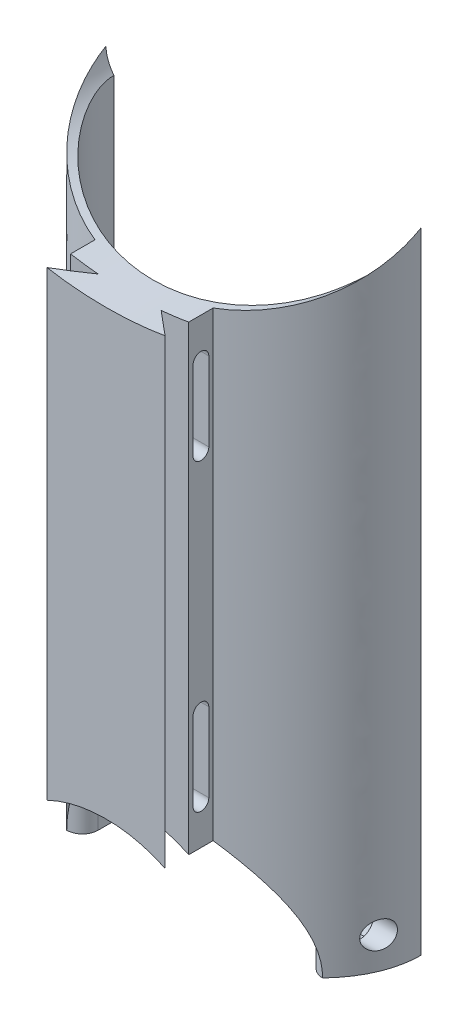
SolidWorks part; units mm, degrees
material "PLA"
ref_plane "Front Plane" through (0, 0, 0) normal (0, 0, 1) x (1, 0, 0)
ref_plane "Top Plane" through (0, 0, 0) normal (0, 1, 0) x (1, 0, 0)
ref_plane "Right Plane" through (0, 0, 0) normal (1, 0, 0) x (0, 0, -1)
sketch "Sketch1" plane through (0, 0, 0) normal (0, 1, 0) x (1, 0, 0)
  ellipse E0 centre (0, 0) end of major axis (25.4, 0) minor radius 19.05
  dimension "D1" = 50.8
  dimension "D2" = 38.1
extrude "Boss-Extrude1" add sketch "Sketch1" along normal blind 101.6 contours E0
shell "Shell1" thickness 1.27 removed face at (25.4, 101.6, 0) removed face at (25.4, 0, 0)
sketch "Sketch3" plane through (0, 0, 0) normal (0, 0, 1) x (1, 0, 0)
  line L1 (29.1836, -15.0653) -> (-40.8926, -15.0653)
  line L2 (29.1836, -15.0653) -> (29.1836, 142.3871)
  line L3 (29.1836, 142.3871) -> (-40.8926, 142.3871)
  line L4 (-40.8926, -15.0653) -> (-40.8926, 142.3871)
extrude "Cut-Extrude1" cut sketch "Sketch3" against normal up to surface up to face at (25.4, 101.6, 0)
ref_plane "Plane4" through (0, 0, 19.05) normal (0, 0, 1) x (1, 0, 0)
sketch "Sketch4" plane through (0, 0, 19.05) normal (0, 0, 1) x (1, 0, 0)
  line L1 (9.525, 101.6) -> (-9.525, 101.6)
  line L2 (9.525, 101.6) -> (9.525, 0)
  line L3 (9.525, 0) -> (-9.525, 0)
  line L4 (-9.525, 101.6) -> (-9.525, 0)
  line L6 (25.4, 101.6) -> (25.4, 0) construction
  line L7 (-25.4, 0) -> (25.4, 0) construction
  line L8 (25.4, 101.6) -> (-25.4, 101.6) construction
  dimension "D1" = 19.05
  dimension "D4" = 15.875
extrude "Boss-Extrude2" add sketch "Sketch4" against normal up to surface (1.3902 mm away) up to face at (0, 50.8, 9.525)
sketch "Sketch6" plane through (0, 0, 19.05) normal (0, 0, 1) x (1, 0, 0)
  line L4 (-9.525, 0) -> (9.525, 0)
  line L5 (9.525, 0) -> (9.525, 101.6)
  line L6 (9.525, 101.6) -> (-9.525, 101.6)
  line L7 (-9.525, 101.6) -> (-9.525, 0)
  line L8 (-9.525, 0) -> (9.525, 0)
  line L9 (9.525, 0) -> (9.525, 101.6)
  line L10 (9.525, 101.6) -> (-9.525, 101.6)
  line L11 (-9.525, 101.6) -> (-9.525, 0)
  dimension "D1" = 0
extrude "Boss-Extrude4" add sketch "Sketch6" along normal blind 6.35
sketch "Sketch7" plane through (0, 0, 0) normal (0, -1, 0) x (1, 0, 0)
  line L0 (-9.525, 25.4) -> (-5.08, 21.59)
  line L1 (9.525, 25.4) -> (5.08, 21.59)
  line L2 (-5.08, 21.59) -> (-9.525, 21.59)
  line L3 (-9.525, 17.6598) -> (-9.525, 25.4) construction
  line L4 (-9.525, 21.59) -> (-9.525, 25.4)
  line L5 (5.08, 21.59) -> (9.525, 21.59)
  line L6 (9.525, 17.6598) -> (9.525, 25.4) construction
  line L7 (9.525, 21.59) -> (9.525, 25.4)
  line L8 (-9.525, 25.4) -> (9.525, 25.4) construction
  dimension "D2" = 3.81
  dimension "D3" = 10.16
extrude "Cut-Extrude2" cut sketch "Sketch7" against normal through all
sketch "Sketch8" plane through (0, 0, 19.05) normal (0, 0, 1) x (1, 0, 0)
  line L0 (25.4, 101.6) -> (25.4, 0) construction
  line L1 (-25.4, 0) -> (-25.4, 101.6) construction
  line L3 (9.525, 101.6) -> (-9.525, 101.6) construction
  ellipse E0 centre (0, 0) end of major axis (-20.6375, 0) minor radius 19.05
  ellipse E1 centre (0, 101.6) end of major axis (25.4, 101.6) minor radius 11.1125
  point P7 (0, 0)
  dimension "D1" = 38.1
  dimension "D2" = 41.275
  dimension "D3" = 22.225
extrude "Cut-Extrude3" cut sketch "Sketch8" against normal through all both and the other way through all
sketch "Sketch10" plane through (9.525, 0, 0) normal (1, 0, 0) x (0, 0, -1)
  line L0 (-19.6215, 23.2496) -> (-19.6215, 35.9496) construction
  line L2 (-20.8915, 23.2496) -> (-20.8915, 35.9496)
  line L3 (-18.3515, 23.2496) -> (-18.3515, 35.9496)
  line L4 (-17.6598, 16.8996) -> (-21.59, 16.8996) construction
  line L6 (-21.59, 91.2984) -> (-21.59, 16.8996) construction
  line L7 (-19.6215, 72.2484) -> (-19.6215, 84.9484) construction
  line L8 (-20.8915, 72.2484) -> (-20.8915, 84.9484)
  line L9 (-18.3515, 72.2484) -> (-18.3515, 84.9484)
  line L10 (-21.59, 91.2984) -> (-17.6598, 91.2984) construction
  arc A0 (-20.8915, 23.2496) -> (-18.3515, 23.2496) centre (-19.6215, 23.2496) ccw
  arc A1 (-18.3515, 35.9496) -> (-20.8915, 35.9496) centre (-19.6215, 35.9496) ccw
  arc A2 (-20.8915, 72.2484) -> (-18.3515, 72.2484) centre (-19.6215, 72.2484) ccw
  arc A3 (-18.3515, 84.9484) -> (-20.8915, 84.9484) centre (-19.6215, 84.9484) ccw
  point P4 (-19.6215, 29.5996)
  point P13 (-19.6215, 78.5984)
  dimension "D3" = 1.27
  dimension "D6" = 1.27
  dimension "D1" = 12.7
  dimension "D2" = 12.7
  dimension "D4" = 1.9685
  dimension "D5" = 12.7
  dimension "D7" = 12.7
extrude "Cut-Extrude4" cut sketch "Sketch10" against normal through all
ref_plane "Plane7" through (20.6375, 0, 0) normal (1, 0, 0) x (0, 0, -1)
ref_plane "Plane8" through (18.0975, 0, 0) normal (1, 0, 0) x (0, 0, -1)
sketch "Sketch14" plane through (18.0975, 0, 0) normal (1, 0, 0) x (0, 0, -1)
  line L1 (-11.1054, 0) -> (0, 0)
  line L2 (-11.1054, 0) -> (-11.1054, 10.16)
  line L3 (-11.1054, 10.16) -> (0, 10.16)
  line L4 (0, 0) -> (0, 10.16)
  dimension "D1" = 10.16
extrude "Boss-Extrude7" add sketch "Sketch14" along normal up to body separate body
sketch "Sketch15" plane through (18.0975, 0, 0) normal (-1, 0, 0) x (0, 0, 1)
  line L2 (11.1054, 10.16) -> (11.1054, 0) construction
  line L3 (11.1054, 0) -> (0, 0) construction
  circle A0 centre (5.5555, 5.08) radius 2.159
  dimension "D1" = 4.318
  dimension "D2" = 5.5499
  dimension "D3" = 5.08
extrude "Cut-Extrude7" cut sketch "Sketch15" against normal through all
sketch "Sketch16" plane through (18.0975, 0, 0) normal (-1, 0, 0) x (0, 0, 1)
  line L0 (0, 10.16) -> (11.1054, 10.16) construction
  line L1 (7.5719, 1.5875) -> (9.5883, 5.08)
  line L2 (9.5883, 5.08) -> (7.5719, 8.5725)
  line L3 (7.5719, 8.5725) -> (3.5391, 8.5725)
  line L4 (3.5391, 8.5725) -> (1.5227, 5.08)
  line L5 (1.5227, 5.08) -> (3.5391, 1.5875)
  line L6 (3.5391, 1.5875) -> (7.5719, 1.5875)
  circle A0 centre (5.5555, 5.08) radius 3.4925 construction
  dimension "D1" = 6.985
extrude "Cut-Extrude8" cut sketch "Sketch16" against normal blind 3.048
mirror "Mirror5" about plane through (0, 0, 0) normal (1, 0, 0) of "Cut-Extrude7", "Boss-Extrude7", "Cut-Extrude8"
fillet "Fillet2" radius 2.54 2 edges at (18.0975, 5.08, 11.1054) (-18.0975, 5.08, 11.1054)
